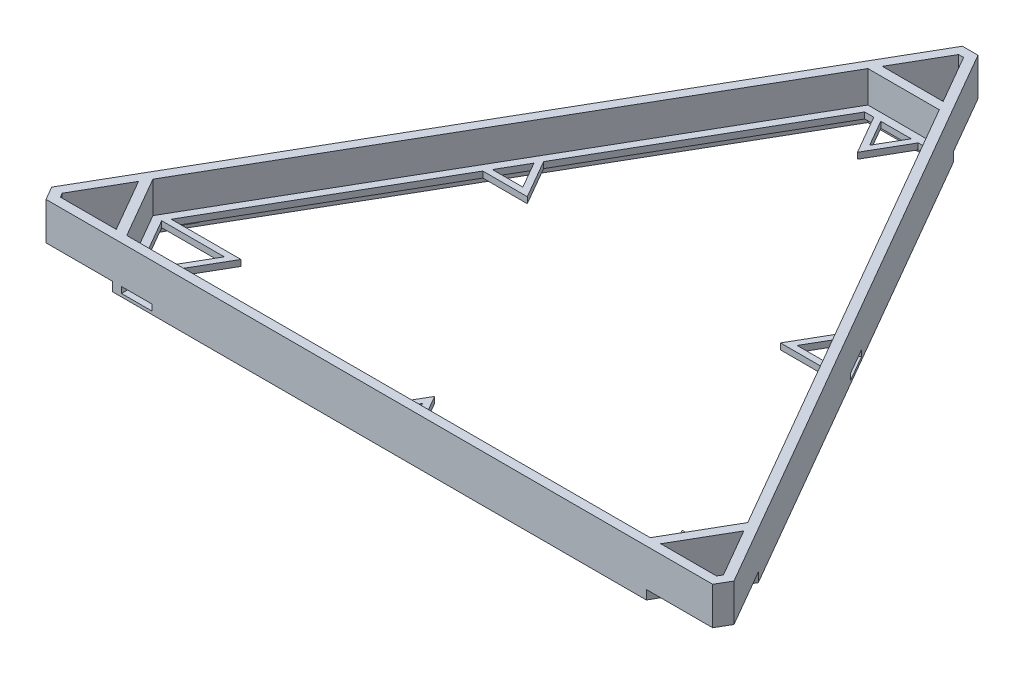
SolidWorks part; units mm, degrees
ref_plane "Front Plane" through (0, 0, 0) normal (0, 0, 1) x (1, 0, 0)
ref_plane "Top Plane" through (0, 0, 0) normal (0, 1, 0) x (1, 0, 0)
ref_plane "Right Plane" through (0, 0, 0) normal (1, 0, 0) x (0, 0, -1)
sketch "Sketch1" plane through (0, 0, 0) normal (0, 1, 0) x (1, 0, 0)
  line L17 (-4, 192.2576) -> (111, -6.9282) construction
  line L24 (4, 192.2576) -> (-111, -6.9282) construction
  line L25 (-115, 0) -> (115, 0) construction
  line L26 (0, -4.4282) -> (0, -1.4282) construction
  line L27 (-113, -3.4641) -> (-107, 0) construction
  line L28 (0, 192.2576) -> (0, 185.3294) construction
  line L29 (113, -3.4641) -> (107, 0) construction
  line L31 (-107.8246, -1.4282) -> (-108.6491, 0)
  line L39 (109.5566, -4.4282) -> (-109.5566, -4.4282)
  line L40 (-0.8246, 186.7576) -> (0.8246, 186.7576)
  line L41 (-109.5566, -4.4282) -> (-112.1132, 0)
  line L42 (-2.5566, 189.7576) -> (-112.1132, 0)
  line L43 (109.5566, -4.4282) -> (112.1132, 0)
  line L44 (-2.5566, 189.7576) -> (2.5566, 189.7576)
  line L45 (2.5566, 189.7576) -> (112.1132, 0)
  line L47 (108.6491, 0) -> (107.8246, -1.4282)
  line L50 (-99.4737, 15.8923) -> (-89.4737, -1.4282)
  line L51 (-107.8246, -1.4282) -> (-89.4737, -1.4282)
  line L52 (-99.4737, 15.8923) -> (-108.6491, 0)
  line L54 (89.4737, -1.4282) -> (107.8246, -1.4282)
  line L56 (89.4737, -1.4282) -> (99.4737, 15.8923)
  line L57 (99.4737, 15.8923) -> (108.6491, 0)
  line L58 (0, -1.4282) -> (0, 1.0718) construction
  line L59 (54.7369, 93.3788) -> (52.5718, 92.1288) construction
  line L62 (-10, 170.8653) -> (10, 170.8653)
  line L63 (-10, 170.8653) -> (-0.8246, 186.7576)
  line L64 (0.8246, 186.7576) -> (10, 170.8653)
  line L65 (94.4737, 7.2321) -> (91.8756, 8.7321) construction
  line L66 (-11.7321, 167.8653) -> (11.7321, 167.8653)
  line L67 (97.7417, 18.8923) -> (86.0096, -1.4282)
  line L68 (97.7417, 18.8923) -> (11.7321, 167.8653)
  line L69 (-54.7369, 93.3788) -> (-52.5718, 92.1288) construction
  line L71 (-94.4737, 7.2321) -> (-91.8756, 8.7321) construction
  line L72 (-97.7417, 18.8923) -> (-86.0096, -1.4282)
  line L73 (-86.0096, -1.4282) -> (86.0096, -1.4282)
  line L74 (-97.7417, 18.8923) -> (-11.7321, 167.8653)
  line L79 (91.8756, 8.7321) -> (89.7106, 9.9821) construction
  line L81 (0, 167.8653) -> (0, 165.3653) construction
  line L97 (-94.8549, 18.8923) -> (-84.5662, 1.0718)
  line L100 (-94.8549, 18.8923) -> (-74.2776, 18.8923)
  line L106 (-84.5662, 1.0718) -> (-74.2776, 18.8923)
  line L108 (50.0718, 96.4589) -> (55.0718, 87.7987)
  line L109 (41.6077, 85.7987) -> (56.2265, 85.7987)
  line L111 (50.0718, 96.4589) -> (45.0718, 87.7987)
  line L112 (45.0718, 87.7987) -> (55.0718, 87.7987)
  line L115 (56.2265, 85.7987) -> (94.8549, 18.8923)
  line L116 (48.9171, 98.4589) -> (10.2887, 165.3653)
  line L117 (41.6077, 85.7987) -> (48.9171, 98.4589)
  line L118 (-5, 165.3653) -> (5, 165.3653)
  line L121 (-55.0718, 87.7987) -> (-50.0718, 96.4589)
  line L122 (-5, 165.3653) -> (0, 156.7051)
  line L123 (5, 165.3653) -> (0, 156.7051)
  line L125 (0, 152.7051) -> (7.3094, 165.3653)
  line L126 (0, 152.7051) -> (-7.3094, 165.3653)
  line L127 (-10.2887, 165.3653) -> (-7.3094, 165.3653)
  line L128 (7.3094, 165.3653) -> (10.2887, 165.3653)
  line L129 (-50.0718, 96.4589) -> (-45.0718, 87.7987)
  line L130 (-55.0718, 87.7987) -> (-45.0718, 87.7987)
  line L131 (-48.9171, 98.4589) -> (-10.2887, 165.3653)
  line L132 (-41.6077, 85.7987) -> (-48.9171, 98.4589)
  line L133 (-41.6077, 85.7987) -> (-56.2265, 85.7987)
  line L134 (5, 1.0718) -> (-5, 1.0718)
  line L135 (-2.5, 5.4019) -> (-4.2321, 6.4019) construction
  line L136 (-5, 1.0718) -> (0, 9.7321)
  line L137 (0, 9.7321) -> (5, 1.0718)
  line L138 (2.5, 5.4019) -> (4.2321, 6.4019) construction
  line L139 (0, 13.7321) -> (-7.3094, 1.0718)
  line L143 (84.5662, 1.0718) -> (7.3094, 1.0718)
  line L144 (0, 13.7321) -> (7.3094, 1.0718)
  line L145 (92.2106, 14.3122) -> (87.2106, 5.6519)
  line L146 (84.7106, 9.9821) -> (82.9785, 8.9821) construction
  line L147 (87.2106, 5.6519) -> (82.2106, 14.3122)
  line L148 (82.2106, 14.3122) -> (92.2106, 14.3122)
  line L149 (87.2106, 14.3122) -> (87.2106, 16.3122) construction
  line L150 (94.8549, 18.8923) -> (93.3653, 16.3122)
  line L151 (78.7465, 16.3122) -> (86.0559, 3.6519)
  line L152 (78.7465, 16.3122) -> (93.3653, 16.3122)
  line L153 (86.0559, 3.6519) -> (84.5662, 1.0718)
  line L154 (-82.2568, 1.0718) -> (-7.3094, 1.0718)
  line L155 (-93.7002, 20.8923) -> (-56.2265, 85.7987)
  line L156 (-70.8135, 20.8923) -> (-93.7002, 20.8923)
  line L159 (-70.8135, 20.8923) -> (-82.2568, 1.0718)
  point P18 (0, -1.4282)
  point P41 (0, 167.8653)
  point P44 (91.8756, 8.7321)
  point P51 (-91.8756, 8.7321)
  point P55 (0, 1.0718)
  point P57 (-52.5718, 92.1288)
  point P61 (52.5718, 92.1288)
  point P65 (52.5718, 92.1288)
  point P69 (89.7106, 9.9821)
  point P74 (0, 165.3653)
  point P79 (0, 165.3653)
  point P89 (-52.5718, 92.1288)
  point P92 (0, 1.0718)
  point P97 (-45.8397, 93.1288)
  point P100 (-50.0718, 85.7987)
  point P106 (-4.2321, 6.4019)
  point P109 (4.2321, 6.4019)
  point P110 (89.7106, 9.9821)
  point P119 (82.9785, 8.9821)
  point P121 (-84.5662, 20.8923)
  point P122 (87.2106, 16.3122)
  dimension "D1" = 8
  dimension "D2" = 8
  dimension "D3" = 8
  dimension "D4" = 230
  dimension "D5" = 230
  dimension "D6" = 230
  dimension "D7" = 3
  dimension "D8" = 3
  dimension "D9" = 3
  dimension "D10" = 2.5
  dimension "D11" = 2.5
  dimension "D12" = 2.5
  dimension "D14" = 2.5
  dimension "D15" = 2.5
  dimension "D17" = 10
  dimension "D18" = 10
  dimension "D19" = 10
  dimension "D20" = 10
  dimension "D21" = 2
  dimension "D22" = 2
  dimension "D23" = 10
  dimension "D24" = 2
  dimension "D25" = 2
extrude "Boss-Extrude1" add sketch "Sketch1" along normal blind 12.38 contours L45 L43 L39 L41 L42 L44 | L74 L66 L68 L67 L73 L72 | L52 L31 L51 L50 | L57 L47 L54 L56 | L64 L62 L63 L40
extrude "Boss-Extrude2" add sketch "Sketch1<4>" along normal blind 2 contours L74 L72 L73 L67 L68 L66 region at (0, 0, -167.6067)
sketch "Sketch1<4>" plane through (0, 0, 0) normal (0, 1, 0) x (1, 0, 0) same geometry as "Sketch1"
sketch "Sketch2" plane through (0, 0, 0) normal (0, -1, 0) x (1, 0, 0)
  line L24 (-2.5566, -189.7576) -> (-112.1132, 0) construction
  line L25 (109.5566, 4.4282) -> (-109.5566, 4.4282) construction
  line L27 (2.5566, -189.7576) -> (112.1132, 0) construction
  line L33 (-89.4737, 1.4282) -> (-101.2058, -18.8923) construction
  line L34 (-89.4737, 1.4282) -> (-87.7417, 4.4282) construction
  line L35 (-11.7321, -167.8653) -> (11.7321, -167.8653)
  line L36 (89.4737, 1.4282) -> (87.7417, 4.4282) construction
  line L37 (99.4737, -15.8923) -> (101.2058, -18.8923) construction
  line L38 (86.0096, 1.4282) -> (97.7417, -18.8923)
  line L40 (101.2058, -18.8923) -> (87.7417, 4.4282)
  line L42 (-10, -170.8653) -> (-13.4641, -170.8653) construction
  line L43 (10, -170.8653) -> (13.4641, -170.8653) construction
  line L44 (87.7417, 4.4282) -> (-87.7417, 4.4282)
  line L45 (-97.7417, -18.8923) -> (-86.0096, 1.4282)
  line L46 (57.3349, -94.8788) -> (54.7369, -93.3788) construction
  line L47 (0, 4.4282) -> (0, 1.4282) construction
  line L48 (-87.7417, 4.4282) -> (-101.2058, -18.8923)
  line L49 (11.7321, -167.8653) -> (97.7417, -18.8923)
  line L50 (-86.0096, 1.4282) -> (86.0096, 1.4282)
  line L51 (-57.3349, -94.8788) -> (-54.7369, -93.3788) construction
  line L52 (-11.7321, -167.8653) -> (-97.7417, -18.8923)
  line L53 (-101.2058, -18.8923) -> (-13.4641, -170.8653)
  line L54 (-13.4641, -170.8653) -> (13.4641, -170.8653)
  line L55 (13.4641, -170.8653) -> (101.2058, -18.8923)
  point P66 (0, -167.8653)
  point P68 (-91.8756, -8.7321)
  point P72 (54.7369, -93.3788)
  point P75 (0, 1.4282)
  point P80 (-54.7369, -93.3788)
  dimension "D4" = 3
  dimension "D5" = 3
  dimension "D6" = 3
extrude "Boss-Extrude3" add sketch "Sketch2" along normal blind 3
sketch "Sketch4" plane through (0, 0, 4.4282) normal (0, 0, 1) x (1, 0, 0)
  line L1 (-84.7417, 0) -> (-84.7417, -2)
  line L2 (-97.7417, 0) -> (-11.7321, 0) construction
  line L3 (-84.7417, -2) -> (-74.7417, -2)
  line L4 (-74.7417, -2) -> (-74.7417, 0)
  line L5 (-74.7417, 0) -> (-84.7417, 0)
  line L6 (-2.5566, 0) -> (-112.1132, 0) construction
  line L7 (-87.7417, 0) -> (-84.7417, 0) construction
  dimension "D1" = 3
  dimension "D2" = 2
  dimension "D3" = 10
extrude "Cut-Extrude1" cut sketch "Sketch4" against normal blind 6
sketch "Sketch5" plane through (-84.0849, 0, -48.5465) normal (-0.866, 0, -0.5) x (-0.5, 0, 0.866)
  line L0 (34.2417, 0) -> (31.2417, 0) construction
  line L1 (-50.9434, 0) -> (58.6132, 0) construction
  line L2 (31.2417, 0) -> (31.2417, -2)
  line L3 (31.2417, -2) -> (21.2417, -2)
  line L4 (21.2417, -2) -> (21.2417, 0)
  line L5 (21.2417, 0) -> (31.2417, 0)
  dimension "D1" = 3
  dimension "D2" = 2
  dimension "D3" = 10
extrude "Cut-Extrude2" cut sketch "Sketch5" against normal blind 6
sketch "Sketch6" plane through (84.0849, 0, -48.5465) normal (0.866, 0, -0.5) x (-0.5, 0, -0.866)
  line L0 (-34.2417, 0) -> (141.2417, 0) construction
  line L1 (58.5, 0) -> (48.5, 0)
  line L2 (48.5, 0) -> (48.5, -2)
  line L3 (48.5, -2) -> (58.5, -2)
  line L4 (58.5, -2) -> (58.5, 0)
  point P8 (53.5, 0)
  dimension "D1" = 10
  dimension "D2" = 2
extrude "Cut-Extrude3" cut sketch "Sketch6" against normal blind 6
